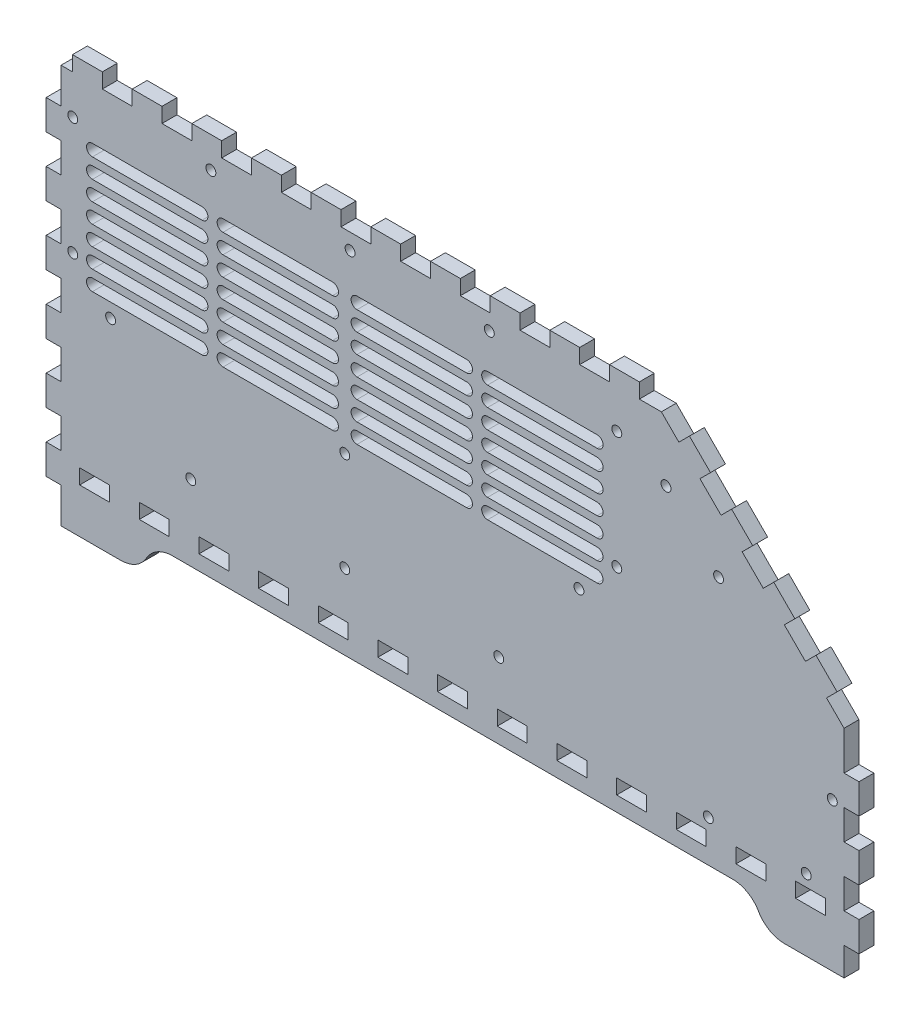
SolidWorks part; units mm, degrees
ref_plane "Front Plane" through (0, 0, 0) normal (0, 0, 1) x (1, 0, 0)
ref_plane "Top Plane" through (0, 0, 0) normal (0, 1, 0) x (1, 0, 0)
ref_plane "Right Plane" through (0, 0, 0) normal (1, 0, 0) x (0, 0, -1)
sketch "Model" plane through (0, 0, 0) normal (0, 0, 1) x (1, 0, 0)
  line L4 (28.9553, 40.0032) -> (23.2406, 40.0032)
  line L5 (23.2406, 40.0032) -> (23.2406, 45.7179)
  line L6 (23.2406, 45.7179) -> (34.67, 45.7179)
  line L7 (34.67, 45.7179) -> (34.67, 40.0032)
  line L8 (34.67, 40.0032) -> (28.9553, 40.0032)
  line L9 (51.8156, 40.0032) -> (46.0996, 40.0032)
  line L10 (46.0996, 40.0032) -> (46.0996, 45.7179)
  line L11 (46.0996, 45.7179) -> (57.5303, 45.7179)
  line L12 (57.5303, 45.7179) -> (57.5303, 40.0032)
  line L13 (57.5303, 40.0032) -> (51.8156, 40.0032)
  line L14 (74.6746, 40.0032) -> (68.9599, 40.0032)
  line L15 (68.9599, 40.0032) -> (68.9599, 45.7179)
  line L16 (68.9599, 45.7179) -> (80.3906, 45.7179)
  line L17 (80.3906, 45.7179) -> (80.3906, 40.0032)
  line L18 (80.3906, 40.0032) -> (74.6746, 40.0032)
  line L19 (97.5349, 40.0032) -> (91.8199, 40.0032)
  line L20 (91.8199, 40.0032) -> (91.8199, 45.7179)
  line L21 (91.8199, 45.7179) -> (103.25, 45.7179)
  line L22 (103.25, 45.7179) -> (103.25, 40.0032)
  line L23 (103.25, 40.0032) -> (97.5349, 40.0032)
  line L24 (120.395, 40.0032) -> (114.68, 40.0032)
  line L25 (114.68, 40.0032) -> (114.68, 45.7179)
  line L26 (114.68, 45.7179) -> (126.11, 45.7179)
  line L27 (126.11, 45.7179) -> (126.11, 40.0032)
  line L28 (126.11, 40.0032) -> (120.395, 40.0032)
  line L29 (143.255, 40.0032) -> (137.541, 40.0032)
  line L30 (137.541, 40.0032) -> (137.541, 45.7179)
  line L31 (137.541, 45.7179) -> (148.97, 45.7179)
  line L32 (148.97, 45.7179) -> (148.97, 40.0032)
  line L33 (148.97, 40.0032) -> (143.255, 40.0032)
  line L34 (166.116, 40.0032) -> (160.4, 40.0032)
  line L35 (160.4, 40.0032) -> (160.4, 45.7179)
  line L36 (160.4, 45.7179) -> (171.83, 45.7179)
  line L37 (171.83, 45.7179) -> (171.83, 40.0032)
  line L38 (171.83, 40.0032) -> (166.116, 40.0032)
  line L39 (188.975, 40.0032) -> (183.26, 40.0032)
  line L40 (183.26, 40.0032) -> (183.26, 45.7179)
  line L41 (183.26, 45.7179) -> (194.691, 45.7179)
  line L42 (194.691, 45.7179) -> (194.691, 40.0032)
  line L43 (194.691, 40.0032) -> (188.975, 40.0032)
  line L44 (211.835, 40.0032) -> (206.12, 40.0032)
  line L45 (206.12, 40.0032) -> (206.12, 45.7179)
  line L46 (206.12, 45.7179) -> (217.55, 45.7179)
  line L47 (217.55, 45.7179) -> (217.55, 40.0032)
  line L48 (217.55, 40.0032) -> (211.835, 40.0032)
  line L49 (234.695, 40.0032) -> (228.98, 40.0032)
  line L50 (228.98, 40.0032) -> (228.98, 45.7179)
  line L51 (228.98, 45.7179) -> (240.41, 45.7179)
  line L52 (240.41, 45.7179) -> (240.41, 40.0032)
  line L53 (240.41, 40.0032) -> (234.695, 40.0032)
  line L54 (257.555, 40.0032) -> (251.841, 40.0032)
  line L55 (251.841, 40.0032) -> (251.841, 45.7179)
  line L56 (251.841, 45.7179) -> (263.27, 45.7179)
  line L57 (263.27, 45.7179) -> (263.27, 40.0032)
  line L58 (263.27, 40.0032) -> (257.555, 40.0032)
  line L59 (280.416, 40.0032) -> (274.7, 40.0032)
  line L60 (274.7, 40.0032) -> (274.7, 45.7179)
  line L61 (274.7, 45.7179) -> (286.13, 45.7179)
  line L62 (286.13, 45.7179) -> (286.13, 40.0032)
  line L63 (286.13, 40.0032) -> (280.416, 40.0032)
  line L64 (303.275, 40.0032) -> (297.56, 40.0032)
  line L65 (297.56, 40.0032) -> (297.56, 45.7179)
  line L66 (297.56, 45.7179) -> (308.991, 45.7179)
  line L67 (308.991, 45.7179) -> (308.991, 40.0032)
  line L68 (308.991, 40.0032) -> (303.275, 40.0032)
  line L69 (16.1148, 22.8575) -> (38.9749, 22.8575)
  line L70 (38.9749, 22.8575) -> (39.3485, 22.8575)
  line L71 (39.3485, 22.8575) -> (40.4689, 22.9567)
  line L72 (40.4689, 22.9567) -> (41.9322, 23.2475)
  line L73 (41.9322, 23.2475) -> (43.3447, 23.7271)
  line L74 (43.3447, 23.7271) -> (44.366, 24.2025)
  line L75 (44.366, 24.2025) -> (44.6899, 24.3885)
  line L76 (44.6899, 24.3885) -> (44.8511, 24.4822)
  line L77 (44.8511, 24.4822) -> (45.3263, 24.7854)
  line L78 (45.3263, 24.7854) -> (45.9341, 25.2222)
  line L79 (45.9341, 25.2222) -> (46.5116, 25.6963)
  line L80 (46.5116, 25.6963) -> (47.056, 26.2062)
  line L81 (47.056, 26.2062) -> (47.5657, 26.7505)
  line L82 (47.5657, 26.7505) -> (48.0399, 27.3279)
  line L83 (48.0399, 27.3279) -> (48.4766, 27.9356)
  line L84 (48.4766, 27.9356) -> (48.7796, 28.411)
  line L85 (48.7796, 28.411) -> (48.8735, 28.5722)
  line L86 (48.8735, 28.5722) -> (48.9673, 28.7348)
  line L87 (48.9673, 28.7348) -> (49.2689, 29.2103)
  line L88 (49.2689, 29.2103) -> (49.7057, 29.818)
  line L89 (49.7057, 29.818) -> (50.1798, 30.3954)
  line L90 (50.1798, 30.3954) -> (50.6899, 30.9397)
  line L91 (50.6899, 30.9397) -> (51.2339, 31.4496)
  line L92 (51.2339, 31.4496) -> (51.8114, 31.9236)
  line L93 (51.8114, 31.9236) -> (52.4192, 32.3605)
  line L94 (52.4192, 32.3605) -> (52.8948, 32.6622)
  line L95 (52.8948, 32.6622) -> (53.0571, 32.756)
  line L96 (53.0571, 32.756) -> (53.3799, 32.9434)
  line L97 (53.3799, 32.9434) -> (54.4008, 33.4188)
  line L98 (54.4008, 33.4188) -> (55.8133, 33.8983)
  line L99 (55.8133, 33.8983) -> (57.2766, 34.1891)
  line L100 (57.2766, 34.1891) -> (58.3971, 34.287)
  line L101 (58.3971, 34.287) -> (58.7721, 34.287)
  line L102 (58.7721, 34.287) -> (273.458, 34.287)
  line L103 (273.458, 34.287) -> (273.831, 34.287)
  line L104 (273.831, 34.287) -> (274.952, 34.1891)
  line L105 (274.952, 34.1891) -> (276.415, 33.8983)
  line L106 (276.415, 33.8983) -> (277.828, 33.4188)
  line L107 (277.828, 33.4188) -> (278.849, 32.9434)
  line L108 (278.849, 32.9434) -> (279.172, 32.756)
  line L109 (279.172, 32.756) -> (279.334, 32.6636)
  line L110 (279.334, 32.6636) -> (279.809, 32.3605)
  line L111 (279.809, 32.3605) -> (280.417, 31.9236)
  line L112 (280.417, 31.9236) -> (280.995, 31.4496)
  line L113 (280.995, 31.4496) -> (281.539, 30.9397)
  line L114 (281.539, 30.9397) -> (282.049, 30.3954)
  line L115 (282.049, 30.3954) -> (282.523, 29.818)
  line L116 (282.523, 29.818) -> (282.96, 29.2103)
  line L117 (282.96, 29.2103) -> (283.263, 28.7348)
  line L118 (283.263, 28.7348) -> (283.356, 28.5722)
  line L119 (283.356, 28.5722) -> (283.449, 28.411)
  line L120 (283.449, 28.411) -> (283.752, 27.9356)
  line L121 (283.752, 27.9356) -> (284.189, 27.3279)
  line L122 (284.189, 27.3279) -> (284.663, 26.7505)
  line L123 (284.663, 26.7505) -> (285.172, 26.2062)
  line L124 (285.172, 26.2062) -> (285.717, 25.6963)
  line L125 (285.717, 25.6963) -> (286.294, 25.2222)
  line L126 (286.294, 25.2222) -> (286.902, 24.7854)
  line L127 (286.902, 24.7854) -> (287.377, 24.4822)
  line L128 (287.377, 24.4822) -> (287.54, 24.3885)
  line L129 (287.54, 24.3885) -> (287.862, 24.2025)
  line L130 (287.862, 24.2025) -> (288.884, 23.7271)
  line L131 (288.884, 23.7271) -> (290.296, 23.2475)
  line L132 (290.296, 23.2475) -> (291.76, 22.9567)
  line L133 (291.76, 22.9567) -> (292.88, 22.8575)
  line L134 (292.88, 22.8575) -> (293.255, 22.8575)
  line L135 (293.255, 22.8575) -> (316.115, 22.8575)
  line L136 (316.115, 22.8575) -> (316.115, 33.6917)
  line L137 (316.115, 33.6917) -> (321.83, 33.6917)
  line L138 (321.83, 33.6917) -> (321.83, 45.1224)
  line L139 (321.83, 45.1224) -> (316.115, 45.1224)
  line L140 (316.115, 45.1224) -> (316.115, 56.552)
  line L141 (316.115, 56.552) -> (321.83, 56.552)
  line L142 (321.83, 56.552) -> (321.83, 67.9813)
  line L143 (321.83, 67.9813) -> (316.115, 67.9813)
  line L144 (316.115, 67.9813) -> (316.115, 79.412)
  line L145 (316.115, 79.412) -> (321.83, 79.412)
  line L146 (321.83, 79.412) -> (321.83, 90.8417)
  line L147 (321.83, 90.8417) -> (316.115, 90.8417)
  line L148 (316.115, 90.8417) -> (316.115, 101.677)
  line L149 (316.115, 101.677) -> (316.115, 105.718)
  line L150 (316.115, 105.718) -> (309.403, 112.43)
  line L151 (309.403, 112.43) -> (313.444, 116.47)
  line L152 (313.444, 116.47) -> (305.362, 124.553)
  line L153 (305.362, 124.553) -> (301.321, 120.512)
  line L154 (301.321, 120.512) -> (293.238, 128.595)
  line L155 (293.238, 128.595) -> (297.28, 132.635)
  line L156 (297.28, 132.635) -> (289.198, 140.717)
  line L157 (289.198, 140.717) -> (285.156, 136.677)
  line L158 (285.156, 136.677) -> (277.074, 144.759)
  line L159 (277.074, 144.759) -> (281.114, 148.801)
  line L160 (281.114, 148.801) -> (273.032, 156.881)
  line L161 (273.032, 156.881) -> (268.992, 152.841)
  line L162 (268.992, 152.841) -> (260.91, 160.923)
  line L163 (260.91, 160.923) -> (264.951, 164.963)
  line L164 (264.951, 164.963) -> (256.869, 173.046)
  line L165 (256.869, 173.046) -> (252.827, 169.005)
  line L166 (252.827, 169.005) -> (246.115, 175.718)
  line L167 (246.115, 175.718) -> (242.074, 175.718)
  line L168 (242.074, 175.718) -> (237.68, 175.718)
  line L169 (237.68, 175.718) -> (237.68, 181.433)
  line L170 (237.68, 181.433) -> (226.249, 181.433)
  line L171 (226.249, 181.433) -> (226.249, 175.718)
  line L172 (226.249, 175.718) -> (214.82, 175.718)
  line L173 (214.82, 175.718) -> (214.82, 181.433)
  line L174 (214.82, 181.433) -> (203.389, 181.433)
  line L175 (203.389, 181.433) -> (203.389, 175.718)
  line L176 (203.389, 175.718) -> (191.959, 175.718)
  line L177 (191.959, 175.718) -> (191.959, 181.433)
  line L178 (191.959, 181.433) -> (180.53, 181.433)
  line L179 (180.53, 181.433) -> (180.53, 175.718)
  line L180 (180.53, 175.718) -> (169.099, 175.718)
  line L181 (169.099, 175.718) -> (169.099, 181.433)
  line L182 (169.099, 181.433) -> (157.67, 181.433)
  line L183 (157.67, 181.433) -> (157.67, 175.718)
  line L184 (157.67, 175.718) -> (146.239, 175.718)
  line L185 (146.239, 175.718) -> (146.239, 181.433)
  line L186 (146.239, 181.433) -> (134.809, 181.433)
  line L187 (134.809, 181.433) -> (134.809, 175.718)
  line L188 (134.809, 175.718) -> (123.38, 175.718)
  line L189 (123.38, 175.718) -> (123.38, 181.433)
  line L190 (123.38, 181.433) -> (111.949, 181.433)
  line L191 (111.949, 181.433) -> (111.949, 175.718)
  line L192 (111.949, 175.718) -> (100.52, 175.718)
  line L193 (100.52, 175.718) -> (100.52, 181.433)
  line L194 (100.52, 181.433) -> (89.0887, 181.433)
  line L195 (89.0887, 181.433) -> (89.0887, 175.718)
  line L196 (89.0887, 175.718) -> (77.6594, 175.718)
  line L197 (77.6594, 175.718) -> (77.6594, 181.433)
  line L198 (77.6594, 181.433) -> (66.2298, 181.433)
  line L199 (66.2298, 181.433) -> (66.2298, 175.718)
  line L200 (66.2298, 175.718) -> (54.7991, 175.718)
  line L201 (54.7991, 175.718) -> (54.7991, 181.433)
  line L202 (54.7991, 181.433) -> (43.3698, 181.433)
  line L203 (43.3698, 181.433) -> (43.3698, 175.718)
  line L204 (43.3698, 175.718) -> (31.9388, 175.718)
  line L205 (31.9388, 175.718) -> (31.9388, 181.433)
  line L206 (31.9388, 181.433) -> (20.5093, 181.433)
  line L207 (20.5093, 181.433) -> (20.5093, 175.718)
  line L208 (20.5093, 175.718) -> (16.1148, 175.718)
  line L209 (16.1148, 175.718) -> (16.1148, 162.153)
  line L210 (16.1148, 162.153) -> (10.4001, 162.153)
  line L211 (10.4001, 162.153) -> (10.4001, 150.723)
  line L212 (10.4001, 150.723) -> (16.1148, 150.723)
  line L213 (16.1148, 150.723) -> (16.1148, 139.292)
  line L214 (16.1148, 139.292) -> (10.4001, 139.292)
  line L215 (10.4001, 139.292) -> (10.4001, 127.863)
  line L216 (10.4001, 127.863) -> (16.1148, 127.863)
  line L217 (16.1148, 127.863) -> (16.1148, 116.433)
  line L218 (16.1148, 116.433) -> (10.4001, 116.433)
  line L219 (10.4001, 116.433) -> (10.4001, 105.003)
  line L220 (10.4001, 105.003) -> (16.1148, 105.003)
  line L221 (16.1148, 105.003) -> (16.1148, 93.5729)
  line L222 (16.1148, 93.5729) -> (10.4001, 93.5729)
  line L223 (10.4001, 93.5729) -> (10.4001, 82.1422)
  line L224 (10.4001, 82.1422) -> (16.1148, 82.1422)
  line L225 (16.1148, 82.1422) -> (16.1148, 70.7125)
  line L226 (16.1148, 70.7125) -> (10.4001, 70.7125)
  line L227 (10.4001, 70.7125) -> (10.4001, 59.2832)
  line L228 (10.4001, 59.2832) -> (16.1148, 59.2832)
  line L229 (16.1148, 59.2832) -> (16.1148, 47.8525)
  line L230 (16.1148, 47.8525) -> (10.4001, 47.8525)
  line L231 (10.4001, 47.8525) -> (10.4001, 36.4229)
  line L232 (10.4001, 36.4229) -> (16.1148, 36.4229)
  line L233 (16.1148, 36.4229) -> (16.1148, 22.8575)
extrude "Boss-Extrude1" add sketch "Model" along normal blind 5.715
sketch "Sketch1" plane through (0, 0, 0) normal (0, 0, -1) x (-1, 0, 0)
  line L7 (-175.5198, 162.6093) -> (-175.5198, 104.7182) construction
  line L8 (-124.8352, 164.2324) -> (-124.8352, 104.7182) construction
  line L9 (-74.1507, 162.6093) -> (-74.1507, 104.7182) construction
  line L10 (-221.5358, 153.5609) -> (-179.5358, 153.5609) construction
  line L11 (-221.5358, 155.8109) -> (-179.5358, 155.8109)
  line L12 (-221.5358, 151.3109) -> (-179.5358, 151.3109)
  line L13 (-225.5519, 161.0072) -> (-175.5198, 162.6093) construction
  line L14 (-175.5198, 162.6093) -> (-124.8352, 164.2324) construction
  line L15 (-124.8352, 164.2324) -> (-74.1507, 162.6093) construction
  line L16 (-74.1507, 162.6093) -> (-24.1152, 167.4577) construction
  line L17 (-200.5358, 161.8083) -> (-200.5358, 104.7182) construction
  line L18 (-221.5358, 143.8609) -> (-179.5358, 143.8609)
  line L19 (-221.5358, 148.3609) -> (-179.5358, 148.3609)
  line L20 (-221.5358, 146.1109) -> (-179.5358, 146.1109) construction
  line L21 (-221.5358, 136.4109) -> (-179.5358, 136.4109)
  line L22 (-221.5358, 140.9109) -> (-179.5358, 140.9109)
  line L23 (-221.5358, 138.6609) -> (-179.5358, 138.6609) construction
  line L24 (-221.5358, 128.9609) -> (-179.5358, 128.9609)
  line L25 (-221.5358, 133.4609) -> (-179.5358, 133.4609)
  line L26 (-221.5358, 131.2109) -> (-179.5358, 131.2109) construction
  line L27 (-221.5358, 121.5109) -> (-179.5358, 121.5109)
  line L28 (-221.5358, 126.0109) -> (-179.5358, 126.0109)
  line L29 (-221.5358, 123.7609) -> (-179.5358, 123.7609) construction
  line L30 (-221.5358, 114.0609) -> (-179.5358, 114.0609)
  line L31 (-221.5358, 118.5609) -> (-179.5358, 118.5609)
  line L32 (-221.5358, 116.3109) -> (-179.5358, 116.3109) construction
  line L33 (-221.5358, 106.6109) -> (-179.5358, 106.6109)
  line L34 (-221.5358, 111.1109) -> (-179.5358, 111.1109)
  line L35 (-221.5358, 108.8609) -> (-179.5358, 108.8609) construction
  line L36 (-129.5037, 108.8609) -> (-171.5037, 108.8609) construction
  line L37 (-129.5037, 111.1109) -> (-171.5037, 111.1109)
  line L38 (-129.5037, 106.6109) -> (-171.5037, 106.6109)
  line L39 (-129.5037, 116.3109) -> (-171.5037, 116.3109) construction
  line L40 (-129.5037, 118.5609) -> (-171.5037, 118.5609)
  line L41 (-129.5037, 114.0609) -> (-171.5037, 114.0609)
  line L42 (-129.5037, 123.7609) -> (-171.5037, 123.7609) construction
  line L43 (-129.5037, 126.0109) -> (-171.5037, 126.0109)
  line L44 (-129.5037, 121.5109) -> (-171.5037, 121.5109)
  line L45 (-129.5037, 131.2109) -> (-171.5037, 131.2109) construction
  line L46 (-129.5037, 133.4609) -> (-171.5037, 133.4609)
  line L47 (-129.5037, 128.9609) -> (-171.5037, 128.9609)
  line L48 (-129.5037, 138.6609) -> (-171.5037, 138.6609) construction
  line L49 (-129.5037, 140.9109) -> (-171.5037, 140.9109)
  line L50 (-129.5037, 136.4109) -> (-171.5037, 136.4109)
  line L51 (-129.5037, 146.1109) -> (-171.5037, 146.1109) construction
  line L52 (-129.5037, 148.3609) -> (-171.5037, 148.3609)
  line L53 (-129.5037, 143.8609) -> (-171.5037, 143.8609)
  line L54 (-129.5037, 153.5609) -> (-171.5037, 153.5609) construction
  line L55 (-129.5037, 155.8109) -> (-171.5037, 155.8109)
  line L56 (-129.5037, 151.3109) -> (-171.5037, 151.3109)
  line L57 (-28.1346, 153.5609) -> (-70.1346, 153.5609) construction
  line L58 (-28.1346, 155.8109) -> (-70.1346, 155.8109)
  line L59 (-28.1346, 151.3109) -> (-70.1346, 151.3109)
  line L60 (-28.1346, 146.1109) -> (-70.1346, 146.1109) construction
  line L61 (-28.1346, 148.3609) -> (-70.1346, 148.3609)
  line L62 (-28.1346, 143.8609) -> (-70.1346, 143.8609)
  line L63 (-28.1346, 138.6609) -> (-70.1346, 138.6609) construction
  line L64 (-28.1346, 140.9109) -> (-70.1346, 140.9109)
  line L65 (-28.1346, 136.4109) -> (-70.1346, 136.4109)
  line L66 (-28.1346, 131.2109) -> (-70.1346, 131.2109) construction
  line L67 (-28.1346, 133.4609) -> (-70.1346, 133.4609)
  line L68 (-28.1346, 128.9609) -> (-70.1346, 128.9609)
  line L69 (-28.1346, 123.7609) -> (-70.1346, 123.7609) construction
  line L70 (-28.1346, 126.0109) -> (-70.1346, 126.0109)
  line L71 (-28.1346, 121.5109) -> (-70.1346, 121.5109)
  line L72 (-28.1346, 116.3109) -> (-70.1346, 116.3109) construction
  line L73 (-28.1346, 118.5609) -> (-70.1346, 118.5609)
  line L74 (-28.1346, 114.0609) -> (-70.1346, 114.0609)
  line L75 (-28.1346, 108.8609) -> (-70.1346, 108.8609) construction
  line L76 (-28.1346, 111.1109) -> (-70.1346, 111.1109)
  line L77 (-28.1346, 106.6109) -> (-70.1346, 106.6109)
  line L78 (-120.1667, 108.8609) -> (-78.1667, 108.8609) construction
  line L79 (-120.1667, 111.1109) -> (-78.1667, 111.1109)
  line L80 (-120.1667, 106.6109) -> (-78.1667, 106.6109)
  line L81 (-120.1667, 116.3109) -> (-78.1667, 116.3109) construction
  line L82 (-120.1667, 118.5609) -> (-78.1667, 118.5609)
  line L83 (-120.1667, 114.0609) -> (-78.1667, 114.0609)
  line L84 (-120.1667, 123.7609) -> (-78.1667, 123.7609) construction
  line L85 (-120.1667, 126.0109) -> (-78.1667, 126.0109)
  line L86 (-120.1667, 121.5109) -> (-78.1667, 121.5109)
  line L87 (-120.1667, 131.2109) -> (-78.1667, 131.2109) construction
  line L88 (-120.1667, 133.4609) -> (-78.1667, 133.4609)
  line L89 (-120.1667, 128.9609) -> (-78.1667, 128.9609)
  line L90 (-120.1667, 138.6609) -> (-78.1667, 138.6609) construction
  line L91 (-120.1667, 140.9109) -> (-78.1667, 140.9109)
  line L92 (-120.1667, 136.4109) -> (-78.1667, 136.4109)
  line L93 (-120.1667, 146.1109) -> (-78.1667, 146.1109) construction
  line L94 (-120.1667, 148.3609) -> (-78.1667, 148.3609)
  line L95 (-120.1667, 143.8609) -> (-78.1667, 143.8609)
  line L96 (-120.1667, 153.5609) -> (-78.1667, 153.5609) construction
  line L97 (-120.1667, 155.8109) -> (-78.1667, 155.8109)
  line L98 (-120.1667, 151.3109) -> (-78.1667, 151.3109)
  line L477 (-16.1148, 175.718) -> (-233.5519, 168.7551) construction
  line L478 (-233.5519, 168.7551) -> (-233.5519, 96.7182) construction
  line L479 (-233.5519, 96.7182) -> (-16.119, 96.7182) construction
  line L480 (-16.119, 96.7182) -> (-16.1148, 175.718) construction
  line L482 (-225.5519, 161.0072) -> (-225.5519, 104.7182) construction
  line L483 (-225.5519, 104.7182) -> (-24.1186, 104.7182) construction
  line L484 (-24.1186, 104.7182) -> (-24.1152, 167.4577) construction
  line L486 (-24.1152, 167.4577) -> (-225.5519, 161.0072) construction
  arc A0 (-221.5358, 155.8109) -> (-221.5358, 151.3109) centre (-221.5358, 153.5609) ccw
  arc A1 (-179.5358, 151.3109) -> (-179.5358, 155.8109) centre (-179.5358, 153.5609) ccw
  arc A2 (-221.5358, 148.3609) -> (-221.5358, 143.8609) centre (-221.5358, 146.1109) ccw
  arc A3 (-179.5358, 143.8609) -> (-179.5358, 148.3609) centre (-179.5358, 146.1109) ccw
  arc A4 (-221.5358, 140.9109) -> (-221.5358, 136.4109) centre (-221.5358, 138.6609) ccw
  arc A5 (-179.5358, 136.4109) -> (-179.5358, 140.9109) centre (-179.5358, 138.6609) ccw
  arc A6 (-221.5358, 133.4609) -> (-221.5358, 128.9609) centre (-221.5358, 131.2109) ccw
  arc A7 (-179.5358, 128.9609) -> (-179.5358, 133.4609) centre (-179.5358, 131.2109) ccw
  arc A8 (-221.5358, 126.0109) -> (-221.5358, 121.5109) centre (-221.5358, 123.7609) ccw
  arc A9 (-179.5358, 121.5109) -> (-179.5358, 126.0109) centre (-179.5358, 123.7609) ccw
  arc A10 (-221.5358, 118.5609) -> (-221.5358, 114.0609) centre (-221.5358, 116.3109) ccw
  arc A11 (-179.5358, 114.0609) -> (-179.5358, 118.5609) centre (-179.5358, 116.3109) ccw
  arc A12 (-221.5358, 111.1109) -> (-221.5358, 106.6109) centre (-221.5358, 108.8609) ccw
  arc A13 (-179.5358, 106.6109) -> (-179.5358, 111.1109) centre (-179.5358, 108.8609) ccw
  arc A14 (-129.5037, 111.1109) -> (-129.5037, 106.6109) centre (-129.5037, 108.8609) cw
  arc A15 (-171.5037, 106.6109) -> (-171.5037, 111.1109) centre (-171.5037, 108.8609) cw
  arc A16 (-129.5037, 118.5609) -> (-129.5037, 114.0609) centre (-129.5037, 116.3109) cw
  arc A17 (-171.5037, 114.0609) -> (-171.5037, 118.5609) centre (-171.5037, 116.3109) cw
  arc A18 (-129.5037, 126.0109) -> (-129.5037, 121.5109) centre (-129.5037, 123.7609) cw
  arc A19 (-171.5037, 121.5109) -> (-171.5037, 126.0109) centre (-171.5037, 123.7609) cw
  arc A20 (-129.5037, 133.4609) -> (-129.5037, 128.9609) centre (-129.5037, 131.2109) cw
  arc A21 (-171.5037, 128.9609) -> (-171.5037, 133.4609) centre (-171.5037, 131.2109) cw
  arc A22 (-129.5037, 140.9109) -> (-129.5037, 136.4109) centre (-129.5037, 138.6609) cw
  arc A23 (-171.5037, 136.4109) -> (-171.5037, 140.9109) centre (-171.5037, 138.6609) cw
  arc A24 (-129.5037, 148.3609) -> (-129.5037, 143.8609) centre (-129.5037, 146.1109) cw
  arc A25 (-171.5037, 143.8609) -> (-171.5037, 148.3609) centre (-171.5037, 146.1109) cw
  arc A26 (-129.5037, 155.8109) -> (-129.5037, 151.3109) centre (-129.5037, 153.5609) cw
  arc A27 (-171.5037, 151.3109) -> (-171.5037, 155.8109) centre (-171.5037, 153.5609) cw
  arc A28 (-28.1346, 155.8109) -> (-28.1346, 151.3109) centre (-28.1346, 153.5609) cw
  arc A29 (-70.1346, 151.3109) -> (-70.1346, 155.8109) centre (-70.1346, 153.5609) cw
  arc A30 (-28.1346, 148.3609) -> (-28.1346, 143.8609) centre (-28.1346, 146.1109) cw
  arc A31 (-70.1346, 143.8609) -> (-70.1346, 148.3609) centre (-70.1346, 146.1109) cw
  arc A32 (-28.1346, 140.9109) -> (-28.1346, 136.4109) centre (-28.1346, 138.6609) cw
  arc A33 (-70.1346, 136.4109) -> (-70.1346, 140.9109) centre (-70.1346, 138.6609) cw
  arc A34 (-28.1346, 133.4609) -> (-28.1346, 128.9609) centre (-28.1346, 131.2109) cw
  arc A35 (-70.1346, 128.9609) -> (-70.1346, 133.4609) centre (-70.1346, 131.2109) cw
  arc A36 (-28.1346, 126.0109) -> (-28.1346, 121.5109) centre (-28.1346, 123.7609) cw
  arc A37 (-70.1346, 121.5109) -> (-70.1346, 126.0109) centre (-70.1346, 123.7609) cw
  arc A38 (-28.1346, 118.5609) -> (-28.1346, 114.0609) centre (-28.1346, 116.3109) cw
  arc A39 (-70.1346, 114.0609) -> (-70.1346, 118.5609) centre (-70.1346, 116.3109) cw
  arc A40 (-28.1346, 111.1109) -> (-28.1346, 106.6109) centre (-28.1346, 108.8609) cw
  arc A41 (-70.1346, 106.6109) -> (-70.1346, 111.1109) centre (-70.1346, 108.8609) cw
  arc A42 (-120.1667, 111.1109) -> (-120.1667, 106.6109) centre (-120.1667, 108.8609) ccw
  arc A43 (-78.1667, 106.6109) -> (-78.1667, 111.1109) centre (-78.1667, 108.8609) ccw
  arc A44 (-120.1667, 118.5609) -> (-120.1667, 114.0609) centre (-120.1667, 116.3109) ccw
  arc A45 (-78.1667, 114.0609) -> (-78.1667, 118.5609) centre (-78.1667, 116.3109) ccw
  arc A46 (-120.1667, 126.0109) -> (-120.1667, 121.5109) centre (-120.1667, 123.7609) ccw
  arc A47 (-78.1667, 121.5109) -> (-78.1667, 126.0109) centre (-78.1667, 123.7609) ccw
  arc A48 (-120.1667, 133.4609) -> (-120.1667, 128.9609) centre (-120.1667, 131.2109) ccw
  arc A49 (-78.1667, 128.9609) -> (-78.1667, 133.4609) centre (-78.1667, 131.2109) ccw
  arc A50 (-120.1667, 140.9109) -> (-120.1667, 136.4109) centre (-120.1667, 138.6609) ccw
  arc A51 (-78.1667, 136.4109) -> (-78.1667, 140.9109) centre (-78.1667, 138.6609) ccw
  arc A52 (-120.1667, 148.3609) -> (-120.1667, 143.8609) centre (-120.1667, 146.1109) ccw
  arc A53 (-78.1667, 143.8609) -> (-78.1667, 148.3609) centre (-78.1667, 146.1109) ccw
  arc A54 (-120.1667, 155.8109) -> (-120.1667, 151.3109) centre (-120.1667, 153.5609) ccw
  arc A55 (-78.1667, 151.3109) -> (-78.1667, 155.8109) centre (-78.1667, 153.5609) ccw
  point P9 (-200.5358, 153.5609)
  point P20 (-200.5358, 146.1109)
  point P33 (-200.5358, 138.6609)
  point P40 (-200.5358, 131.2109)
  point P47 (-200.5358, 123.7609)
  point P54 (-200.5358, 116.3109)
  point P61 (-200.5358, 108.8609)
  point P68 (-150.5037, 108.8609)
  point P75 (-150.5037, 116.3109)
  point P82 (-150.5037, 123.7609)
  point P89 (-150.5037, 131.2109)
  point P96 (-150.5037, 138.6609)
  point P103 (-150.5037, 146.1109)
  point P110 (-150.5037, 153.5609)
  point P117 (-49.1346, 153.5609)
  point P124 (-49.1346, 146.1109)
  point P131 (-49.1346, 138.6609)
  point P138 (-49.1346, 131.2109)
  point P145 (-49.1346, 123.7609)
  point P152 (-49.1346, 116.3109)
  point P159 (-49.1346, 108.8609)
  point P166 (-99.1667, 108.8609)
  point P173 (-99.1667, 116.3109)
  point P180 (-99.1667, 123.7609)
  point P187 (-99.1667, 131.2109)
  point P194 (-99.1667, 138.6609)
  point P201 (-99.1667, 146.1109)
  point P208 (-99.1667, 153.5609)
  dimension "D4" = 2.25
  dimension "D2" = 42
  dimension "D5" = 50.0321
  dimension "D6" = 7
  dimension "D7" = 7.45
  dimension "D3" = 7.4462
  dimension "D8" = 217.4367
  dimension "D9" = 72
  dimension "D1" = 8
extrude "Cut-Extrude1" cut sketch "Sketch1" against normal through all
sketch "Sketch2" plane through (0, 0, 5.715) normal (0, 0, 1) x (1, 0, 0)
  point P0 (73.5357, 169.5805)
  point P3 (180.2023, 169.5805)
  point P13 (126.869, 169.5805)
sketch "Sketch5" plane through (0, 0, 5.715) normal (0, 0, 1) x (1, 0, 0)
  point P0 (35.1148, 101.2182)
  point P1 (124.8331, 101.2182)
  point P3 (214.5515, 101.2182)
  point P5 (229.0515, 115.7182)
  point P7 (229.0515, 160.7182)
  point P9 (20.6148, 115.7182)
  point P11 (20.6148, 160.7182)
  point P13 (65.8352, 63.2182)
  point P15 (183.8353, 63.2182)
  point P17 (124.8352, 63.2182)
  point P18 (311.618, 79.7182)
  point P20 (301.618, 50.2182)
  point P23 (264.118, 50.2182)
  point P25 (247.8993, 152.0133)
  point P27 (268.0519, 131.8608)
hole_wizard "#6 Clearance Hole1" positions "Sketch3" profile "Sketch4" hole size "#6" standard "ANSI Inch" end condition through all
sketch "Sketch3" plane through (0, 0, 0) normal (0, 0, -1) x (-1, 0, 0)
  point P6 (-126.869, 169.5805)
  point P9 (-73.5357, 169.5805)
  point P18 (-180.2023, 169.5805)
  point P23 (-229.0515, 160.7182)
  point P26 (-229.0515, 115.7182)
  point P29 (-214.5515, 101.2182)
  point P32 (-183.8353, 63.2182)
  point P35 (-124.8352, 63.2182)
  point P38 (-124.8331, 101.2182)
  point P41 (-35.1148, 101.2182)
  point P44 (-20.6148, 115.7182)
  point P47 (-65.8352, 63.2182)
  point P50 (-20.6148, 160.7182)
  point P54 (-311.618, 79.7182)
  point P57 (-301.618, 50.2182)
  point P60 (-264.118, 50.2182)
  point P64 (-268.0519, 131.8608)
  point P67 (-247.8993, 152.0133)
sketch "Sketch4" plane through (126.869, 169.5805, 0) normal (1, 0, 0) x (0, 1, 0)
  line L0 (0, 0) -> (0, 5.715)
  line L1 (0, 5.715) -> (1.8986, 5.715)
  line L2 (1.8986, 5.715) -> (1.8986, 0)
  line L5 (1.8986, 0) -> (0, 0)
  line L11 (0, -6.35) -> (0, 107.95) construction
  dimension "Thru Hole Dia." = 3.7973
  dimension "Thru Hole Depth" = 5.715
